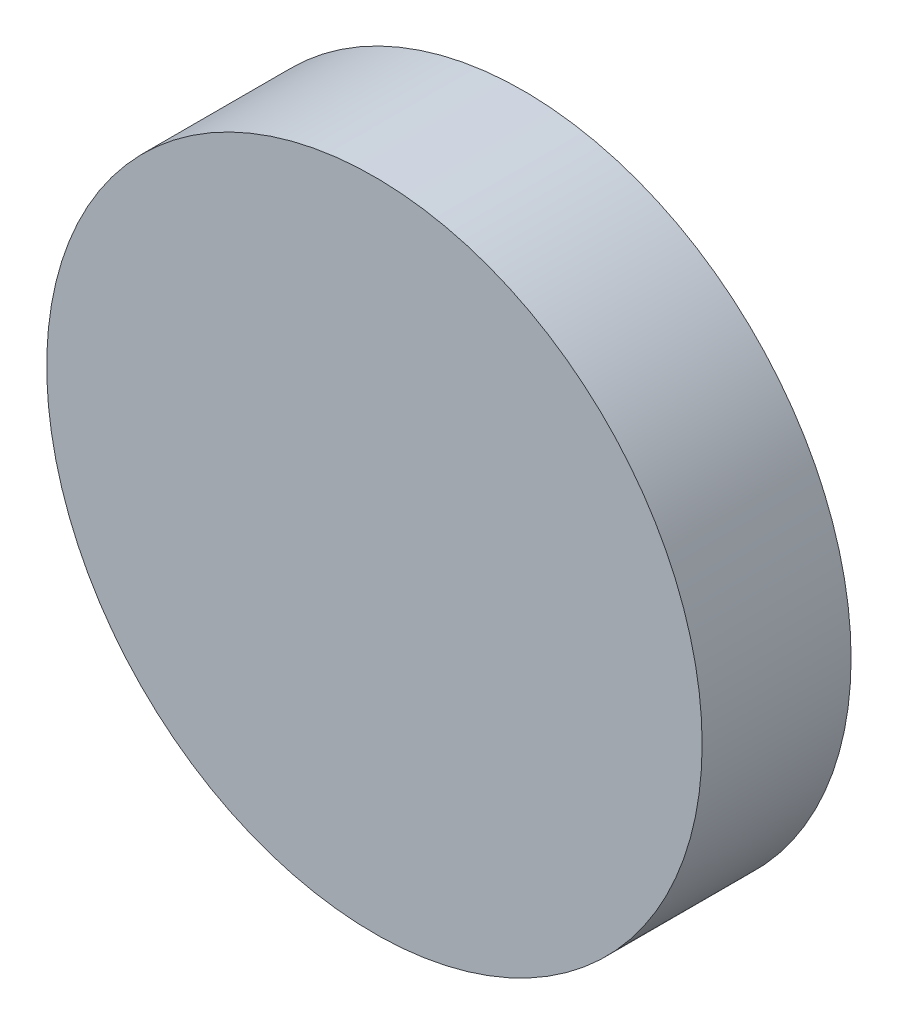
SolidWorks part; units mm, degrees
ref_plane "Front Plane" through (0, 0, 0) normal (0, 0, 1) x (1, 0, 0)
ref_plane "Top Plane" through (0, 0, 0) normal (0, 1, 0) x (1, 0, 0)
ref_plane "Right Plane" through (0, 0, 0) normal (1, 0, 0) x (0, 0, -1)
sketch "Sketch1" plane through (0, 0, 0) normal (0, 0, 1) x (1, 0, 0)
  circle A0 centre (0, 0) radius 8.5
  circle A1 centre (0, 0) radius 11
  dimension "D1" = 17
  dimension "D2" = 22
extrude "Boss-Extrude1" add sketch "Sketch1" along normal blind 5 contours A1
extrude "Cut-Extrude1" cut sketch "Sketch1<3>" along normal blind 3 contours A0
sketch "Sketch1<3>" plane through (0, 0, 0) normal (0, 0, 1) x (1, 0, 0) same geometry as "Sketch1"
